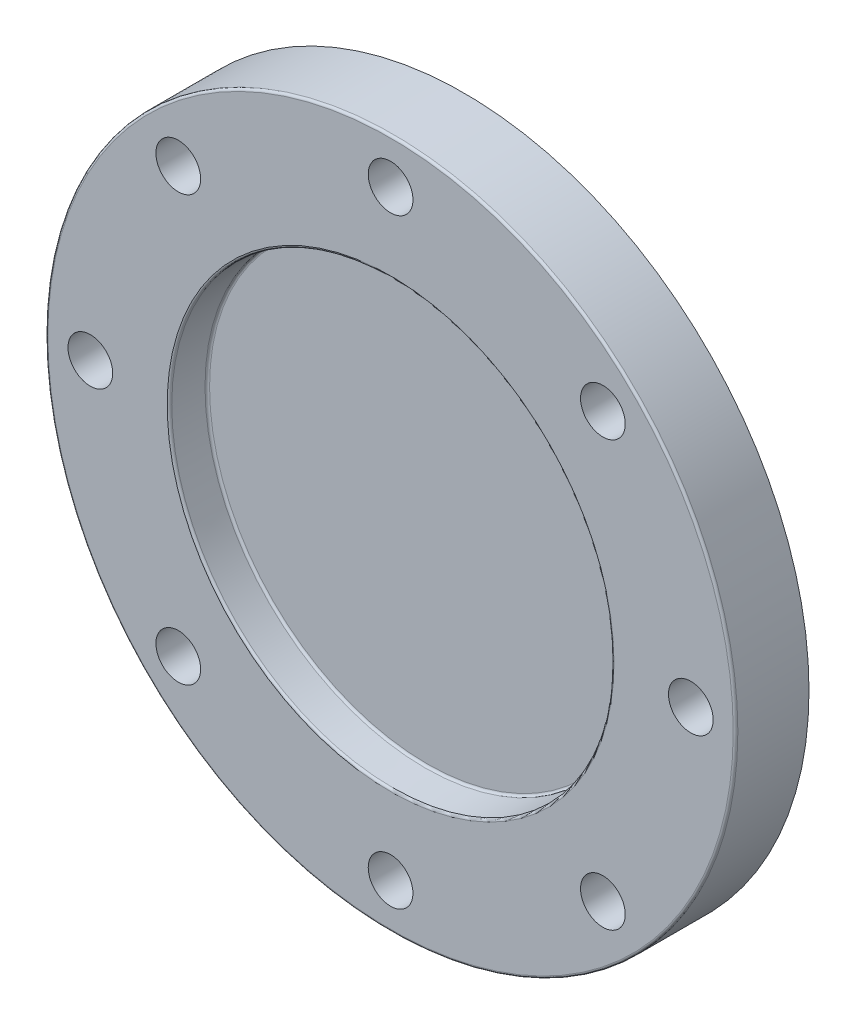
SolidWorks part; units mm, degrees
ref_plane "Front Plane" through (0, 0, 0) normal (0, 0, 1) x (1, 0, 0)
ref_plane "Top Plane" through (0, 0, 0) normal (0, 1, 0) x (1, 0, 0)
ref_plane "Right Plane" through (0, 0, 0) normal (1, 0, 0) x (0, 0, -1)
sketch "Sketch0" plane through (0, 0, 0) normal (1, 0, 0) x (0, 0, -1)
  line L0 (0, 0) -> (-36.5125, 0) construction
  point P3 (-36.5125, 0)
  point P4 (-5.5562, 0)
  dimension "Q" = 36.5125
  dimension "N" = 5.5562
sketch "Sketch1" plane through (0, 0, 0) normal (0, 0, 1) x (1, 0, 0)
  circle A0 centre (0, 0) radius 171.45
  circle A1 centre (0, 0) radius 109.9185 construction
  circle A2 centre (0, 0) radius 149.225 construction
  circle A3 centre (0, 149.225) radius 11.1125 construction
  circle A6 centre (0, 0) radius 109.347 construction
  point P9 (0, 109.9185)
  point P10 (0, 109.347)
  dimension "A" = 342.9
  dimension "B" = 298.45
  dimension "Bolt Hole Size" = 22.225
  dimension "Pipe OD A" = 219.837
  dimension "Pipe OD B" = 218.694
extrude "Extrude1" add sketch "Sketch1" along normal up to vertex (36.5125 mm away) up to point (0, 0, 36.5125)
sketch "Sketch2" plane through (0, 0, 36.5125) normal (0, 0, 1) x (1, 0, 0)
  circle A0 centre (0, 149.225) radius 11.1125 construction
  circle A1 centre (0, 149.225) radius 11.1125
extrude "Extrude2" cut sketch "Sketch2" against normal through all
ref_axis "Axis1" through (0, 0, -1.6272) along (0, 0, 1)
pattern_circular "CirPattern1" count 8 over 360 about axis through (0, 0, -1.6272) along (0, 0, 1) of "Extrude2"
sketch "Sketch3" plane through (0, 0, 0) normal (1, 0, 0) x (0, 0, -1)
  line L0 (-36.5125, 109.9185) -> (-18.2563, 109.347)
  line L1 (-18.2563, 109.347) -> (-18.2562, 0)
  line L2 (0, 0) -> (-36.5125, 0) construction
  line L3 (-18.2562, 0) -> (-36.5125, 0)
  line L4 (-36.5125, 0) -> (-36.5125, 109.9185)
  line L5 (0, 109.347) -> (-18.2563, 109.347) construction
  line L6 (-36.5125, 109.9185) -> (0, 109.9185) construction
revolve "Cut-Revolve1" cut sketch "Sketch3" angle 360 about L3
fillet "Fillet1" radius 1.1545 3 edges at (171.45, 0, 36.5125) (0, 109.347, 18.2563) (0, 109.9185, 36.5125) tangent propagation no
